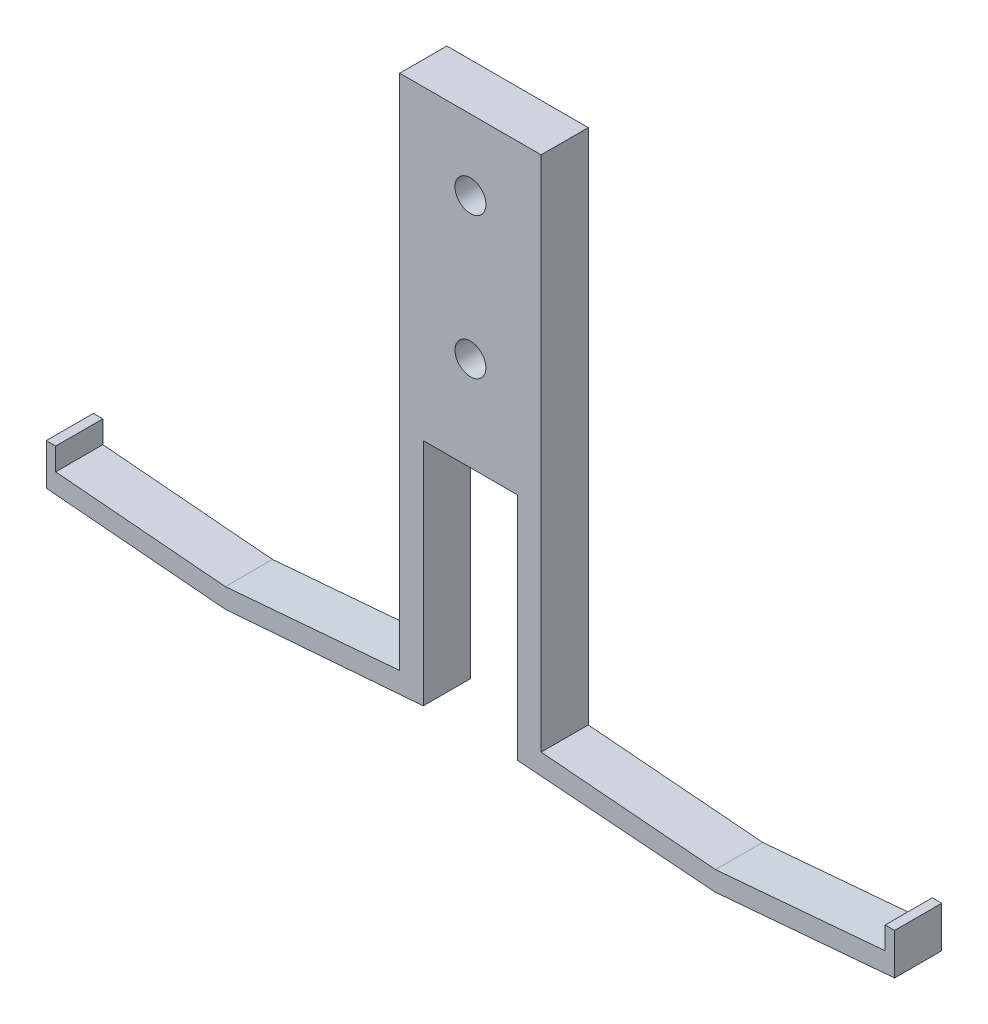
SolidWorks part; units mm, degrees
material "Nylon 6/10"
ref_plane "Front Plane" through (0, 0, 0) normal (0, 0, 1) x (1, 0, 0)
ref_plane "Top Plane" through (0, 0, 0) normal (0, 1, 0) x (1, 0, 0)
ref_plane "Right Plane" through (0, 0, 0) normal (1, 0, 0) x (0, 0, -1)
sketch "Sketch2" plane through (0, 0, 0) normal (0, 0, 1) x (1, 0, 0)
  line L1 (12.7, 0) -> (12.7, -61.918)
  line L2 (12.7, -61.918) -> (66.04, -66.0514)
  line L3 (66.04, -66.0514) -> (114.3, -61.918)
  line L4 (114.3, -61.918) -> (114.3, -50.8114)
  line L5 (111.76, -50.8114) -> (111.76, -56.838)
  line L6 (111.76, -56.838) -> (66.04, -60.7538)
  line L19 (114.3, -50.8114) -> (111.76, -50.8114)
  line L20 (0, 125.2351) -> (0, -75.9356) construction
  line L21 (12.7, 0) -> (-12.7, 0)
  line L22 (0, 0) -> (0, 82.55)
  line L23 (19.05, 82.55) -> (-19.05, 82.55)
  line L24 (19.05, 82.55) -> (19.05, 0)
  line L25 (19.05, 0) -> (19.05, -56.838)
  line L26 (19.05, -56.838) -> (66.04, -60.7538)
  line L27 (-19.05, 0) -> (-19.05, -56.838)
  line L28 (-19.05, 82.55) -> (-19.05, 0)
  line L29 (-12.7, 0) -> (-12.7, -61.918)
  line L30 (-12.7, -61.918) -> (-66.04, -66.0514)
  line L31 (-66.04, -66.0514) -> (-114.3, -61.918)
  line L32 (-114.3, -61.918) -> (-114.3, -50.8114)
  line L33 (-114.3, -50.8114) -> (-111.76, -50.8114)
  line L34 (-111.76, -50.8114) -> (-111.76, -56.838)
  line L35 (-111.76, -56.838) -> (-66.04, -60.7538)
  line L36 (-19.05, -56.838) -> (-66.04, -60.7538)
  dimension "D1" = 19.05
  dimension "D2" = 12.7
  dimension "D3" = 56.838
  dimension "D4" = 3.9158
  dimension "D5" = 61.918
  dimension "D6" = 2.54
  dimension "D7" = 45.72
  dimension "D8" = 46.99
  dimension "D9" = 15.24
  dimension "D10" = 82.55
extrude "Boss-Extrude1" add sketch "Sketch2" along normal blind 12.7 contours L26 L25 L24 L23 L22 L21 L1 L2 L3 L4 L19 L5 L6 | L27 L36 L35 L34 L33 L32 L31 L30 L29 L21 L22 L23 L28 region at (6.35, 1.8747, 0) region at (-6.35, 1.8747, 0)
hole_wizard "21/64 (0.32813) Diameter Hole1" positions "Sketch3" profile "Sketch4" hole size "21/64" standard "ANSI Inch" end condition through all
sketch "Sketch3" plane through (0, 0, 12.7) normal (0, 0, 1) x (1, 0, 0)
  point P0 (0, 25.4)
  point P2 (0, 63.5)
  dimension "D1" = 25.4
  dimension "D2" = 38.1
sketch "Sketch4" plane through (0, 25.4, 12.7) normal (1, 0, 0) x (0, -1, 0)
  line L0 (0, 0) -> (0, 12.7)
  line L1 (0, 12.7) -> (4.1673, 12.7)
  line L2 (4.1673, 12.7) -> (4.1673, 0)
  line L5 (4.1673, 0) -> (0, 0)
  line L11 (0, -6.35) -> (0, 107.95) construction
  dimension "Thru Hole Dia." = 8.3345
  dimension "Thru Hole Depth" = 12.7
